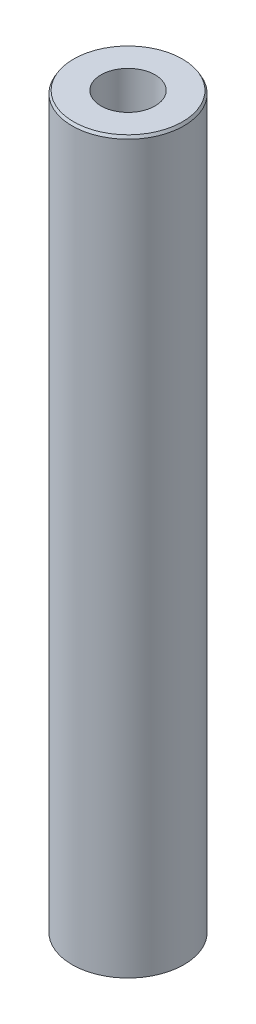
SolidWorks part; units mm, degrees
ref_plane "Front Plane" through (0, 0, 0) normal (0, 0, 1) x (1, 0, 0)
ref_plane "Top Plane" through (0, 0, 0) normal (0, 1, 0) x (1, 0, 0)
ref_plane "Right Plane" through (0, 0, 0) normal (1, 0, 0) x (0, 0, -1)
sketch "Sketch1" plane through (0, 0, 0) normal (0, 1, 0) x (1, 0, 0)
  circle A0 centre (0, 0) radius 42.5
  dimension "SHAFT_OD" = 85
extrude "Boss-Extrude1" add sketch "Sketch1" along normal blind 554.6428
sketch "Sketch2" plane through (0, 0, 0) normal (0, 1, 0) x (1, 0, 0)
  circle A0 centre (0, 0) radius 20.51
  dimension "BORE_D" = 41.0201
extrude "Cut-Extrude1" cut sketch "Sketch2" along normal through all
chamfer "Chamfer1" distance 2.0653 angle 30 2 edges at (0, 554.6428, 42.5) (0, 0, 42.5) first distance on face at (0, 554.6428, 42.5) first distance on face at (0, 0, 20.51)
